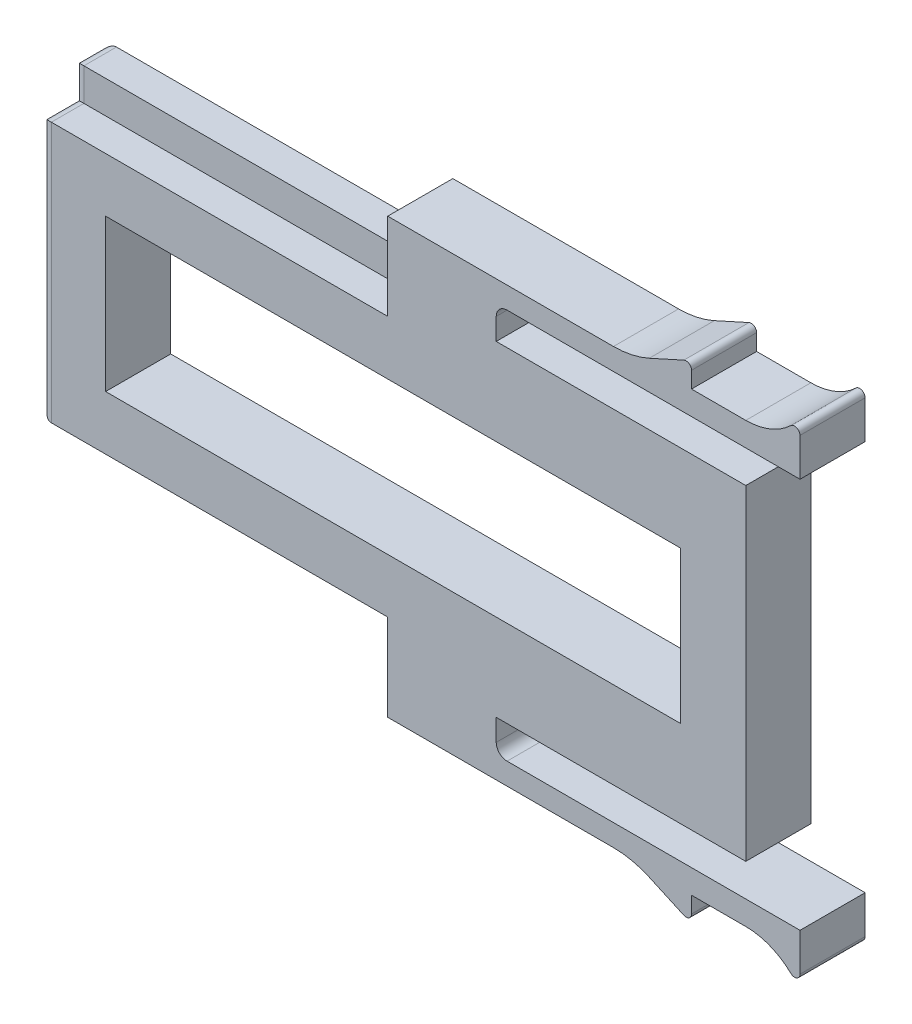
SolidWorks part; units mm, degrees
ref_plane "Front Plane" through (0, 0, 0) normal (1, 0, 0) x (0, 1, 0)
ref_plane "Top Plane" through (0, 0, 0) normal (0, 0, 1) x (0, 1, 0)
ref_plane "Right Plane" through (0, 0, 0) normal (0, 1, 0) x (-1, 0, 0)
sketch "Sketch1" plane through (0, 0, 0) normal (0, 0, 1) x (0, 1, 0)
  line L0 (-15, -9.5) -> (-17, -9.5)
  line L1 (-15, -32.5) -> (15, -32.5)
  line L2 (-15, -32.5) -> (-15, -9.5)
  line L3 (-15, 32.5) -> (15, 32.5)
  line L4 (15, -32.5) -> (15, -9.5)
  line L5 (-15, -32.5) -> (15, 32.5) construction
  line L6 (-15, 32.5) -> (15, -32.5) construction
  line L14 (-21.7, -27.5) -> (-20.2, -27.5)
  line L15 (-18, -10.5) -> (-18, -27.5)
  line L17 (-20, -9.5) -> (-18, -9.5) construction
  line L18 (-15, 32.5) -> (-15, -9.5) construction
  line L19 (0, 32.5) -> (0, -32.5) construction
  line L28 (-20, 0.5) -> (-15, 0.5)
  line L29 (-15, 0.5) -> (-15, 32.5)
  line L40 (15, 32.5) -> (15, 0.5)
  line L41 (-20, -9.5) -> (-20, 0.5)
  line L43 (-20.2, -27.5) -> (-20.2, -32.5)
  line L44 (-18, -27.5) -> (-18, -37.5)
  line L45 (-18, -37.5) -> (-21.5, -37.5)
  line L46 (-20.2, -32.5) -> (-18, -32.5) construction
  line L47 (-18, -27.5) -> (-20.2, -27.5) construction
  line L49 (15, -9.5) -> (17, -9.5)
  line L50 (20, 0.5) -> (15, 0.5)
  line L51 (18, -27.5) -> (20.2, -27.5) construction
  line L60 (-20, -9.5) -> (-20, -20.306)
  line L61 (-20.712, -23.6053) -> (-22.1555, -26.7938)
  line L62 (20.2, -32.5) -> (18, -32.5) construction
  line L63 (20, -9.5) -> (18, -9.5) construction
  line L64 (20.712, -23.6053) -> (22.1555, -26.7938)
  line L65 (20, -9.5) -> (20, -20.306)
  line L66 (18, -37.5) -> (21.5, -37.5)
  line L67 (18, -27.5) -> (18, -37.5)
  line L68 (20.2, -27.5) -> (20.2, -32.5)
  line L69 (20, -9.5) -> (20, 0.5)
  line L70 (18, -10.5) -> (18, -27.5)
  line L71 (21.7, -27.5) -> (20.2, -27.5)
  arc A0 (-21.5, -37.5) -> (-21.8621, -36.6552) centre (-21.5, -37) cw
  arc A1 (-20.2, -32.5) -> (-21.8621, -36.6552) centre (-26.225, -32.5) cw
  arc A4 (-22.1555, -26.7938) -> (-21.7, -27.5) centre (-21.7, -27) ccw
  arc A5 (-20, -20.306) -> (-20.712, -23.6053) centre (-28, -20.306) cw
  arc A6 (-17, -9.5) -> (-18, -10.5) centre (-17, -10.5) ccw
  arc A7 (17, -9.5) -> (18, -10.5) centre (17, -10.5) cw
  arc A8 (20, -20.306) -> (20.712, -23.6053) centre (28, -20.306) ccw
  arc A9 (22.1555, -26.7938) -> (21.7, -27.5) centre (21.7, -27) cw
  arc A10 (20.2, -32.5) -> (21.8621, -36.6552) centre (26.225, -32.5) ccw
  arc A11 (21.5, -37.5) -> (21.8621, -36.6552) centre (21.5, -37) ccw
  point P1 (0, 0)
  point P43 (-22.4752, -27.5)
  point P56 (22.4752, -27.5)
  dimension "D10" = 0.5
  dimension "D5" = 0.5
  dimension "D8" = 8
  dimension "D16" = 1
  dimension "D1" = 30
  dimension "D2" = 65
  dimension "D3" = 18
  dimension "D4" = 10
  dimension "D6" = 5
  dimension "D7" = 2
  dimension "D9" = 5
  dimension "D11" = 2.2
  dimension "D12" = 3.5
  dimension "D13" = 5
  dimension "D14" = 1.5
  dimension "D15" = 3.5
extrude "Boss-Extrude1" add sketch "Sketch1" along normal blind 6
sketch "Sketch4" plane through (-32.5, 0, 0) normal (-1, 0, 0) x (0, -1, 0)
  line L0 (0, 6) -> (0, 0) construction
  line L1 (-15, 6) -> (-12, 6)
  line L2 (-15, 6) -> (-15, 3)
  line L3 (-15, 3) -> (-12, 3)
  line L4 (-12, 6) -> (-12, 3)
  line L5 (-15, 6) -> (15, 6) construction
  line L6 (15, 3) -> (12, 3)
  line L7 (12, 6) -> (12, 3)
  line L8 (15, 6) -> (12, 6)
  line L9 (15, 6) -> (15, 3)
  dimension "D1" = 3
  dimension "D2" = 3
extrude "Cut-Extrude2" cut sketch "Sketch4" against normal up to surface (32 mm away) up to face at (-0.5, -17.5, 3)
fillet "Fillet1" radius 1 8 edges at (-32.5, 0, 6) (-32.5, -12, 4.5) (-32.5, -13.5, 3) (-32.5, -15, 1.5) (-32.5, 0, 0) (-32.5, 15, 1.5) (-32.5, 13.5, 3) (-32.5, 12, 4.5)
sketch "Sketch6" plane through (0, 0, 6) normal (0, 0, 1) x (1, 0, 0)
  line L0 (-31.5, 12) -> (-31.5, -12) construction
  line L1 (-26.5, -7) -> (26.5, -7)
  line L2 (-26.5, -7) -> (-26.5, 7)
  line L3 (-26.5, 7) -> (26.5, 7)
  line L4 (26.5, -7) -> (26.5, 7)
  line L5 (-26.5, -7) -> (26.5, 7) construction
  line L6 (-26.5, 7) -> (26.5, -7) construction
  line L7 (-0.5, 12) -> (-31.5, 12) construction
  point P0 (0, 0)
  dimension "D1" = 5
  dimension "D2" = 5
extrude "Cut-Extrude4" cut sketch "Sketch6" against normal through all
